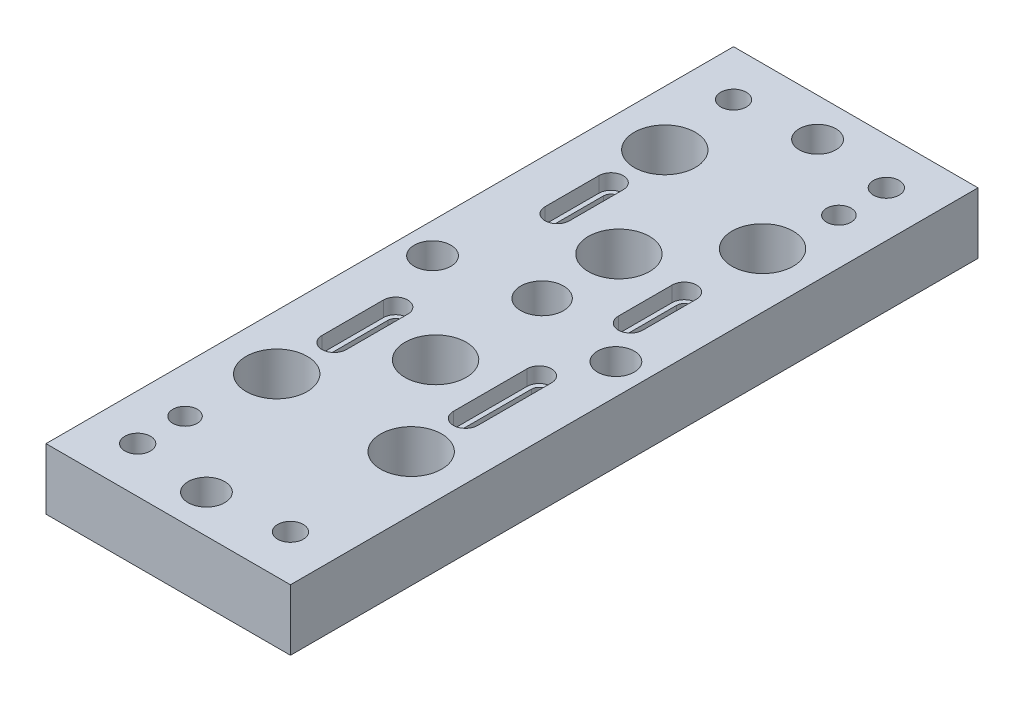
SolidWorks part; units mm, degrees
material "Plain Carbon Steel"
ref_plane "Front Plane" through (0, 0, 0) normal (0, 0, 1) x (1, 0, 0)
ref_plane "Top Plane" through (0, 0, 0) normal (0, 1, 0) x (1, 0, 0)
ref_plane "Right Plane" through (0, 0, 0) normal (1, 0, 0) x (0, 0, -1)
sketch "Sketch1" plane through (0, 0, 0) normal (0, 1, 0) x (1, 0, 0)
  line L1 (-40, -112.5) -> (40, -112.5)
  line L2 (-40, -112.5) -> (-40, 112.5)
  line L3 (-40, 112.5) -> (40, 112.5)
  line L4 (40, -112.5) -> (40, 112.5)
  line L5 (-40, -112.5) -> (40, 112.5) construction
  line L6 (-40, 112.5) -> (40, -112.5) construction
  point P0 (0, 0)
  dimension "D1" = 225
  dimension "D2" = 80
extrude "Boss-Extrude1" add sketch "Sketch1" against normal blind 20
sketch "Sketch2" plane through (0, 0, 0) normal (0, 1, 0) x (1, 0, 0)
  line L4 (24, 17.31) -> (24, 34.91)
  line L5 (19, 34.91) -> (19, 17.31)
  line L6 (24, 17.31) -> (24, 34.91)
  line L7 (19, 34.91) -> (19, 17.31)
  line L10 (24, -36.69) -> (24, -12.59)
  line L11 (19, -12.59) -> (19, -36.69)
  line L12 (24, -36.69) -> (24, -12.59)
  line L13 (19, -12.59) -> (19, -36.69)
  line L16 (-24, -16.59) -> (-24, -36.69)
  line L17 (-19, -36.69) -> (-19, -16.59)
  line L18 (-24, -16.59) -> (-24, -36.69)
  line L19 (-19, -36.69) -> (-19, -16.59)
  line L22 (-24, 53.91) -> (-24, 36.31)
  line L23 (-19, 36.31) -> (-19, 53.91)
  line L24 (-24, 53.91) -> (-24, 36.31)
  line L25 (-19, 36.31) -> (-19, 53.91)
  arc A4 (24, 34.91) -> (19, 34.91) centre (21.5, 34.91) ccw
  arc A5 (19, 17.31) -> (24, 17.31) centre (21.5, 17.31) ccw
  arc A6 (24, 34.91) -> (19, 34.91) centre (21.5, 34.91) ccw
  arc A7 (19, 17.31) -> (24, 17.31) centre (21.5, 17.31) ccw
  arc A10 (24, -12.59) -> (19, -12.59) centre (21.5, -12.59) ccw
  arc A11 (19, -36.69) -> (24, -36.69) centre (21.5, -36.69) ccw
  arc A12 (24, -12.59) -> (19, -12.59) centre (21.5, -12.59) ccw
  arc A13 (19, -36.69) -> (24, -36.69) centre (21.5, -36.69) ccw
  arc A16 (-24, -36.69) -> (-19, -36.69) centre (-21.5, -36.69) ccw
  arc A17 (-19, -16.59) -> (-24, -16.59) centre (-21.5, -16.59) ccw
  arc A18 (-24, -36.69) -> (-19, -36.69) centre (-21.5, -36.69) ccw
  arc A19 (-19, -16.59) -> (-24, -16.59) centre (-21.5, -16.59) ccw
  arc A22 (-24, 36.31) -> (-19, 36.31) centre (-21.5, 36.31) ccw
  arc A23 (-19, 53.91) -> (-24, 53.91) centre (-21.5, 53.91) ccw
  arc A24 (-24, 36.31) -> (-19, 36.31) centre (-21.5, 36.31) ccw
  arc A25 (-19, 53.91) -> (-24, 53.91) centre (-21.5, 53.91) ccw
  dimension "D2" = 0.05
  dimension "D1" = 0.05
  dimension "D3" = 0.05
  dimension "D4" = 0.05
extrude "Cut-Extrude1" cut sketch "Sketch2" against normal up to next
sketch "Sketch3" plane through (0, 0, 0) normal (0, 1, 0) x (1, 0, 0)
  line L4 (-17.5, 36.31) -> (-17.5, 53.91)
  line L5 (-25.5, 53.91) -> (-25.5, 36.31)
  line L6 (-17.5, 36.31) -> (-17.5, 53.91)
  line L7 (-25.5, 53.91) -> (-25.5, 36.31)
  line L10 (25.5, 17.31) -> (25.5, 34.91)
  line L11 (17.5, 34.91) -> (17.5, 17.31)
  line L12 (25.5, 17.31) -> (25.5, 34.91)
  line L13 (17.5, 34.91) -> (17.5, 17.31)
  line L16 (25.5, -36.69) -> (25.5, -12.59)
  line L17 (17.5, -12.59) -> (17.5, -36.69)
  line L18 (25.5, -36.69) -> (25.5, -12.59)
  line L19 (17.5, -12.59) -> (17.5, -36.69)
  line L22 (-25.5, -16.59) -> (-25.5, -36.69)
  line L23 (-17.5, -36.69) -> (-17.5, -16.59)
  line L24 (-25.5, -16.59) -> (-25.5, -36.69)
  line L25 (-17.5, -36.69) -> (-17.5, -16.59)
  arc A4 (-17.5, 53.91) -> (-25.5, 53.91) centre (-21.5, 53.91) ccw
  arc A5 (-25.5, 36.31) -> (-17.5, 36.31) centre (-21.5, 36.31) ccw
  arc A6 (-17.5, 53.91) -> (-25.5, 53.91) centre (-21.5, 53.91) ccw
  arc A7 (-25.5, 36.31) -> (-17.5, 36.31) centre (-21.5, 36.31) ccw
  arc A10 (25.5, 34.91) -> (17.5, 34.91) centre (21.5, 34.91) ccw
  arc A11 (17.5, 17.31) -> (25.5, 17.31) centre (21.5, 17.31) ccw
  arc A12 (25.5, 34.91) -> (17.5, 34.91) centre (21.5, 34.91) ccw
  arc A13 (17.5, 17.31) -> (25.5, 17.31) centre (21.5, 17.31) ccw
  arc A16 (25.5, -12.59) -> (17.5, -12.59) centre (21.5, -12.59) ccw
  arc A17 (17.5, -36.69) -> (25.5, -36.69) centre (21.5, -36.69) ccw
  arc A18 (25.5, -12.59) -> (17.5, -12.59) centre (21.5, -12.59) ccw
  arc A19 (17.5, -36.69) -> (25.5, -36.69) centre (21.5, -36.69) ccw
  arc A22 (-25.5, -36.69) -> (-17.5, -36.69) centre (-21.5, -36.69) ccw
  arc A23 (-17.5, -16.59) -> (-25.5, -16.59) centre (-21.5, -16.59) ccw
  arc A24 (-25.5, -36.69) -> (-17.5, -36.69) centre (-21.5, -36.69) ccw
  arc A25 (-17.5, -16.59) -> (-25.5, -16.59) centre (-21.5, -16.59) ccw
  dimension "D1" = 1.5
  dimension "D2" = 1.5
  dimension "D3" = 1.5
  dimension "D4" = 1.5
extrude "Cut-Extrude2" cut sketch "Sketch3" against normal blind 5
hole_wizard "CBORE for M8 Hex Socket Head Cap Screw1" positions "Sketch7" profile "Sketch6" counterbore size "M8" standard "ISO" end condition through all
sketch "Sketch7" plane through (0, -20, 0) normal (0, -1, 0) x (-1, 0, 0)
  line L0 (-40, -112.5) -> (-40, 112.5) construction
  line L1 (-40, 112.5) -> (40, 112.5) construction
  line L2 (40, 112.5) -> (40, -112.5) construction
  line L3 (40, -112.5) -> (-40, -112.5) construction
  point P0 (-25, 97.5)
  point P2 (25, 97.5)
  point P4 (25, -97.5)
  point P6 (-25, -97.5)
  dimension "D1" = 15
  dimension "D2" = 15
  dimension "D3" = 15
  dimension "D4" = 15
sketch "Sketch6" plane through (25, -20, -97.5) normal (1, 0, 0) x (0, 0, -1)
  line L0 (0, 0) -> (0, 20)
  line L1 (0, 20) -> (4.2, 20)
  line L3 (4.2, 20) -> (4.2, 8.6)
  line L4 (7.5, 8.6) -> (4.2, 8.6)
  line L5 (7.5, 8.6) -> (7.5, 0.025)
  line L6 (7.5, 0.025) -> (7.525, 0)
  line L7 (7.525, 0) -> (0, 0)
  line L8 (-7.5, 0.025) -> (-7.525, 0) construction
  line L11 (0, -6.35) -> (0, 107.95) construction
  dimension "Thru Hole Dia." = 8.4
  dimension "Thru Hole Depth" = 20
  dimension "C'Bore Dia." = 15
  dimension "C'Bore Depth" = 8.6
  dimension "Near C'Sink Dia." = 15.05
  dimension "Near C'Sink Angle" = 90
hole_wizard "Ø8.0mm Dowel Hole1" positions "Sketch12" profile "Sketch9" hole size "Ø8.0" standard "ISO" end condition through all
sketch "Sketch12" plane through (0, -20, 0) normal (0, -1, 0) x (-1, 0, 0)
  line L4 (25, -97.5) -> (25, -82) construction
  line L6 (-25, 97.5) -> (-25, 81.975) construction
  circle A1 centre (25, -97.5) radius 7.5 construction
  circle A3 centre (-25, 97.5) radius 7.525 construction
  point P0 (-25, 81.975)
  point P2 (25, -82)
  dimension "D1" = 8
  dimension "D2" = 8
sketch "Sketch9" plane through (25, -20, -81.975) normal (1, 0, 0) x (0, 0, -1)
  line L0 (0, 0) -> (0, 20)
  line L1 (0, 20) -> (4, 20)
  line L2 (4, 20) -> (4, 0)
  line L5 (4, 0) -> (0, 0)
  line L11 (0, -6.35) -> (0, 107.95) construction
  dimension "Thru Hole Dia." = 8
  dimension "Thru Hole Depth" = 20
sketch "Sketch11" plane through (0, -20, 0) normal (0, -1, 0) x (1, 0, 0)
  circle A0 centre (-22, 55) radius 10
  circle A1 centre (22, 55) radius 10
  circle A2 centre (-22, -72) radius 10
  circle A3 centre (22, -60) radius 10
  circle A4 centre (0, -35) radius 10
  circle A5 centre (0, 25) radius 10
  dimension "D1" = 20
  dimension "D2" = 35
  dimension "D3" = 25
  dimension "D4" = 72
  dimension "D5" = 22
  dimension "D6" = 22
  dimension "D7" = 55
  dimension "D8" = 60
extrude "Cut-Extrude3" cut sketch "Sketch11" against normal through all
sketch "Sketch13" plane through (0, 0, 0) normal (0, 1, 0) x (1, 0, 0)
  circle A0 centre (0, 100) radius 6
  circle A1 centre (0, -100) radius 6
  circle A2 centre (-30, 4) radius 6
  circle A3 centre (30, 4) radius 6
  dimension "D1" = 12
extrude "Cut-Extrude4" cut sketch "Sketch13" against normal up to next
sketch "Sketch14" plane through (0, 0, 0) normal (0, 1, 0) x (1, 0, 0)
  circle A0 centre (0, 9.86) radius 5 construction
  circle A1 centre (0, 9.86) radius 5 construction
  circle A2 centre (0, 9.86) radius 7
  dimension "D1" = 14
extrude "Cut-Extrude5" cut sketch "Sketch14" against normal up to next
